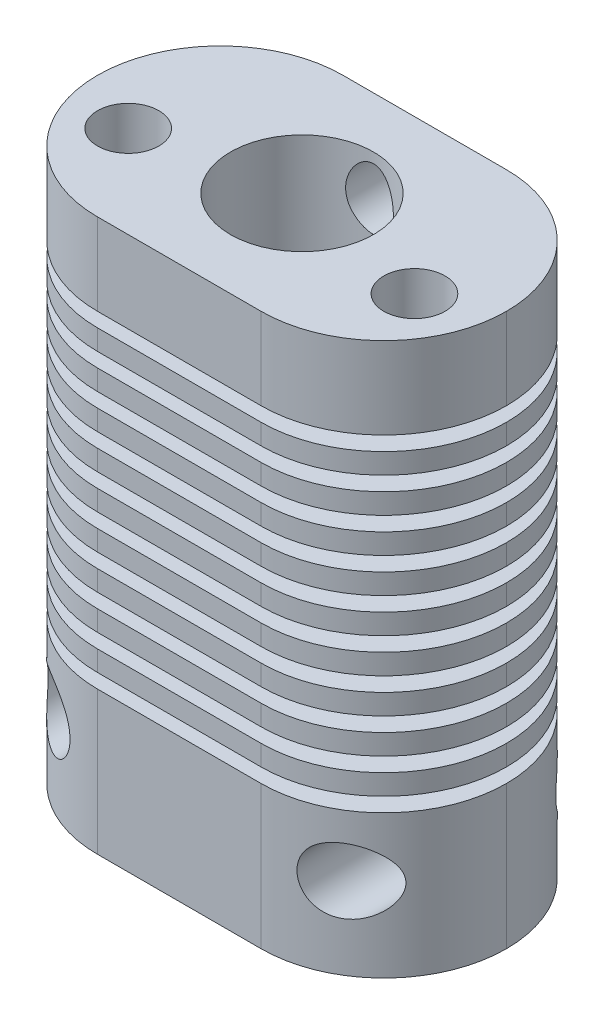
SolidWorks part; units mm, degrees
ref_plane "Płaszczyzna przednia" through (0, 0, 0) normal (0, 0, 1) x (1, 0, 0)
ref_plane "Płaszczyzna górna" through (0, 0, 0) normal (0, 1, 0) x (1, 0, 0)
ref_plane "Płaszczyzna prawa" through (0, 0, 0) normal (1, 0, 0) x (0, 0, -1)
sketch "Szkic1" plane through (0, 0, 0) normal (0, 0, 1) x (1, 0, 0)
  line L1 (0, 0) -> (20, 0)
  line L2 (0, 0) -> (0, 27)
  line L3 (0, 27) -> (20, 27)
  line L4 (20, 0) -> (20, 27)
  dimension "D1" = 27
  dimension "D2" = 20
extrude "Dodanie-wyciągnięcie1" add sketch "Szkic1" along normal blind 12
fillet "Zaokrąglenie2" radius 6 4 edges at (20, 13.5, 0) (20, 13.5, 12) (0, 13.5, 0) (0, 13.5, 12)
ref_plane "Płaszczyzna1" through (10, 0, 0) normal (-1, 0, 0) x (0, 0, 1)
ref_plane "Plane1" through (10, 0, 0) normal (-1, 0, 0) x (0, 0, 1)
sketch "Sketch1" plane through (10, 0, 0) normal (-1, 0, 0) x (0, 0, 1)
  line L0 (0, 27) -> (0, 0)
  line L1 (12, 27) -> (12, 0)
  line L2 (0, 27) -> (12, 27)
  line L3 (12, 0) -> (0, 0)
  line L4 (12, 0) -> (0, 0)
  line L5 (0, 27) -> (12, 27)
  line L6 (12, 27) -> (12, 0)
  line L7 (0, 27) -> (0, 0)
ref_plane "Plane2" through (0, 0, 0) normal (-1, 0, 0) x (0, 0, 1)
sketch "Sketch2" plane through (0, 0, 0) normal (-1, 0, 0) x (0, 0, 1)
  line L0 (6, 0) -> (6, 27)
  line L1 (6, 0) -> (6, 27)
sketch "Sketch3" plane through (10, 0, 0) normal (-1, 0, 0) x (0, 0, 1)
  line L0 (0, 27) -> (12, 27) construction
  line L1 (-4.7141, 23) -> (1.7, 23)
  line L2 (-4.7141, 23) -> (-4.7141, 22.3)
  line L3 (-4.7141, 22.3) -> (1.7, 22.3)
  line L4 (1.7, 23) -> (1.7, 22.3)
  line L5 (6, 0) -> (6, 27) construction
  line L6 (-4.7141, 21.3) -> (-4.7141, 20.6)
  line L7 (-4.7141, 21.3) -> (1.7, 21.3)
  line L8 (1.7, 21.3) -> (1.7, 20.6)
  line L9 (-4.7141, 20.6) -> (1.7, 20.6)
  line L10 (-4.7141, 19.6) -> (-4.7141, 18.9)
  line L11 (-4.7141, 19.6) -> (1.7, 19.6)
  line L12 (1.7, 19.6) -> (1.7, 18.9)
  line L13 (-4.7141, 18.9) -> (1.7, 18.9)
  line L14 (-4.7141, 17.9) -> (-4.7141, 17.2)
  line L15 (-4.7141, 17.9) -> (1.7, 17.9)
  line L16 (1.7, 17.9) -> (1.7, 17.2)
  line L17 (-4.7141, 17.2) -> (1.7, 17.2)
  line L18 (-4.7141, 16.2) -> (-4.7141, 15.5)
  line L19 (-4.7141, 16.2) -> (1.7, 16.2)
  line L20 (1.7, 16.2) -> (1.7, 15.5)
  line L21 (-4.7141, 15.5) -> (1.7, 15.5)
  line L22 (-4.7141, 14.5) -> (-4.7141, 13.8)
  line L23 (-4.7141, 14.5) -> (1.7, 14.5)
  line L24 (1.7, 14.5) -> (1.7, 13.8)
  line L25 (-4.7141, 13.8) -> (1.7, 13.8)
  line L26 (-4.7141, 12.8) -> (-4.7141, 12.1)
  line L27 (-4.7141, 12.8) -> (1.7, 12.8)
  line L28 (1.7, 12.8) -> (1.7, 12.1)
  line L29 (-4.7141, 12.1) -> (1.7, 12.1)
  line L30 (-4.7141, 11.1) -> (-4.7141, 10.4)
  line L31 (-4.7141, 11.1) -> (1.7, 11.1)
  line L32 (1.7, 11.1) -> (1.7, 10.4)
  line L33 (-4.7141, 10.4) -> (1.7, 10.4)
  line L34 (-4.7141, 9.4) -> (-4.7141, 8.7)
  line L35 (-4.7141, 9.4) -> (1.7, 9.4)
  line L36 (1.7, 9.4) -> (1.7, 8.7)
  line L37 (-4.7141, 8.7) -> (1.7, 8.7)
  line L38 (-4.7141, 7.7) -> (-4.7141, 7)
  line L39 (-4.7141, 7.7) -> (1.7, 7.7)
  line L40 (1.7, 7.7) -> (1.7, 7)
  line L41 (-4.7141, 7) -> (1.7, 7)
  line L42 (6, 26.2556) -> (6, -0.7641) construction
  dimension "D1" = 4
  dimension "D2" = 4.3
  dimension "D3" = 0.7
  dimension "D5" = 4.3
  dimension "D4" = 10
revolve "Cut-Revolve1" cut sketch "Sketch3" angle 360 about L42
hole_wizard "Ø3.0mm Dowel Hole2" positions "Sketch5" profile "Sketch7" hole size "Ø3.0" standard "ANSI Metric"
sketch "Sketch5" plane through (0, 0, 0) normal (0, 0, -1) x (-1, 0, 0)
  line L1 (-10, 27) -> (-10, 0) construction
  line L2 (-14, 27) -> (-6, 27) construction
  line L3 (-14, 27) -> (-14, 23) construction
  point P4 (-10, 25)
  dimension "D1" = 2
  dimension "D2" = 4
sketch "Sketch7" plane through (10, 25, 0) normal (1, 0, 0) x (0, 1, 0)
  line L0 (0, 0) -> (0, 3.4013)
  line L1 (0, 3.4013) -> (1.5, 2.5)
  line L2 (1.5, 2.5) -> (1.5, 0)
  line L5 (1.5, 0) -> (0, 0)
  line L10 (0, 3.4013) -> (-1.5, 2.5) construction
  line L11 (0, -6.35) -> (0, 107.95) construction
  dimension "Hole Dia." = 3
  dimension "Hole Depth" = 2.5
  dimension "Drill Angle" = 118
hole_wizard "Ø3.0mm Dowel Hole3" positions "3DSketch1" profile "Sketch8" hole size "Ø3.0" standard "ANSI Metric" end condition through all
sketch3d "3DSketch1"
  line L1 (10, 27, 0) -> (10, 0, 0) construction
  line L2 (6, 0, 0) -> (14, 0, 0) construction
  point P0 (17.15, 4, 0)
  point P2 (2.85, 4, 0)
  dimension "D1" = 14.3
  dimension "D2" = 7.15
  dimension "D3" = 4
sketch "Sketch8" plane through (17.15, 4, 0) normal (1, 0, 0) x (0, 1, 0)
  line L0 (0, 0) -> (0, 12)
  line L1 (0, 12) -> (1.6, 12)
  line L2 (1.6, 12) -> (1.6, 0)
  line L5 (1.6, 0) -> (0, 0)
  line L11 (0, -6.35) -> (0, 107.95) construction
  dimension "Thru Hole Dia." = 3.2
  dimension "Thru Hole Depth" = 12
hole_wizard "Ø6.0mm Dowel Hole1" positions "Sketch9" profile "Sketch10" hole size "Ø6.0" standard "ANSI Metric"
sketch "Sketch9" plane through (0, 27, 0) normal (0, 1, 0) x (1, 0, 0)
  line L0 (14, -12) -> (6, -12) construction
  point P0 (10, -6)
  dimension "D1" = 6
  dimension "D2" = 10
sketch "Sketch10" plane through (10, 27, 6) normal (1, 0, 0) x (0, 0, 1)
  line L0 (0, 0) -> (0, 16.6)
  line L1 (0, 16.6) -> (3.5, 16.6)
  line L2 (3.5, 16.6) -> (3.5, 0)
  line L5 (3.5, 0) -> (0, 0)
  line L10 (0, 16.6) -> (-3.5, 16.6) construction
  line L11 (0, -6.35) -> (0, 107.95) construction
  dimension "Hole Dia." = 7
  dimension "Hole Depth" = 16.6
  dimension "Drill Angle" = 180
hole_wizard "Ø3.0mm Dowel Hole4" positions "Sketch11" profile "Sketch12" hole size "Ø3.0" standard "ANSI Metric"
sketch "Sketch11" plane through (0, 27, 0) normal (0, 1, 0) x (1, 0, 0)
  line L0 (10, 0) -> (10, -12) construction
  circle A0 centre (10, -6) radius 3.5 construction
  point P0 (17, -7.5)
  point P2 (3, -7.5)
  point P5 (0, 0)
  dimension "D1" = 14
  dimension "D2" = 1.5
  dimension "D3" = 7
sketch "Sketch12" plane through (17, 27, 7.5) normal (1, 0, 0) x (0, 0, 1)
  line L0 (0, 0) -> (0, 3.9013)
  line L1 (0, 3.9013) -> (1.5, 3)
  line L2 (1.5, 3) -> (1.5, 0)
  line L5 (1.5, 0) -> (0, 0)
  line L10 (0, 3.9013) -> (-1.5, 3) construction
  line L11 (0, -6.35) -> (0, 107.95) construction
  dimension "Hole Dia." = 3
  dimension "Hole Depth" = 3
  dimension "Drill Angle" = 118
hole_wizard "Ø5.0mm Dowel Hole1" positions "Sketch13" profile "Sketch14" hole size "Ø5.0" standard "ANSI Metric"
sketch "Sketch13" plane through (0, 10.4, 0) normal (0, 1, 0) x (1, 0, 0)
  circle A1 centre (10, -6) radius 3.5 construction
  point P0 (10, -6)
  point P3 (0, 0)
  point P7 (9.9204, -6.0609)
sketch "Sketch14" plane through (10, 10.4, 6) normal (1, 0, 0) x (0, 0, 1)
  line L0 (0, 0) -> (0, 2.4)
  line L1 (0, 2.4) -> (2.5, 2.4)
  line L2 (2.5, 2.4) -> (2.5, 0)
  line L5 (2.5, 0) -> (0, 0)
  line L10 (0, 2.4) -> (-2.5, 2.4) construction
  line L11 (0, -6.35) -> (0, 107.95) construction
  dimension "Hole Dia." = 5
  dimension "Hole Depth" = 2.4
  dimension "Drill Angle" = 180
hole_wizard "Ø10.0mm Dowel Hole3" positions "Sketch15" profile "Sketch16" hole size "Ø10.0" standard "ANSI Metric"
sketch "Sketch15" plane through (0, 0, 0) normal (0, -1, 0) x (-1, 0, 0)
  line L0 (-10, -12) -> (-10, 0) construction
  line L1 (-6, 0) -> (-14, 0) construction
  point P0 (-10, -6)
  dimension "D1" = 6
sketch "Sketch16" plane through (10, 0, 6) normal (1, 0, 0) x (0, 0, -1)
  line L0 (0, 0) -> (0, 9.0043)
  line L1 (0, 9.0043) -> (5, 6)
  line L2 (5, 6) -> (5, 0)
  line L5 (5, 0) -> (0, 0)
  line L10 (0, 9.0043) -> (-5, 6) construction
  line L11 (0, -6.35) -> (0, 107.95) construction
  dimension "Hole Dia." = 10
  dimension "Hole Depth" = 6
  dimension "Drill Angle" = 118
